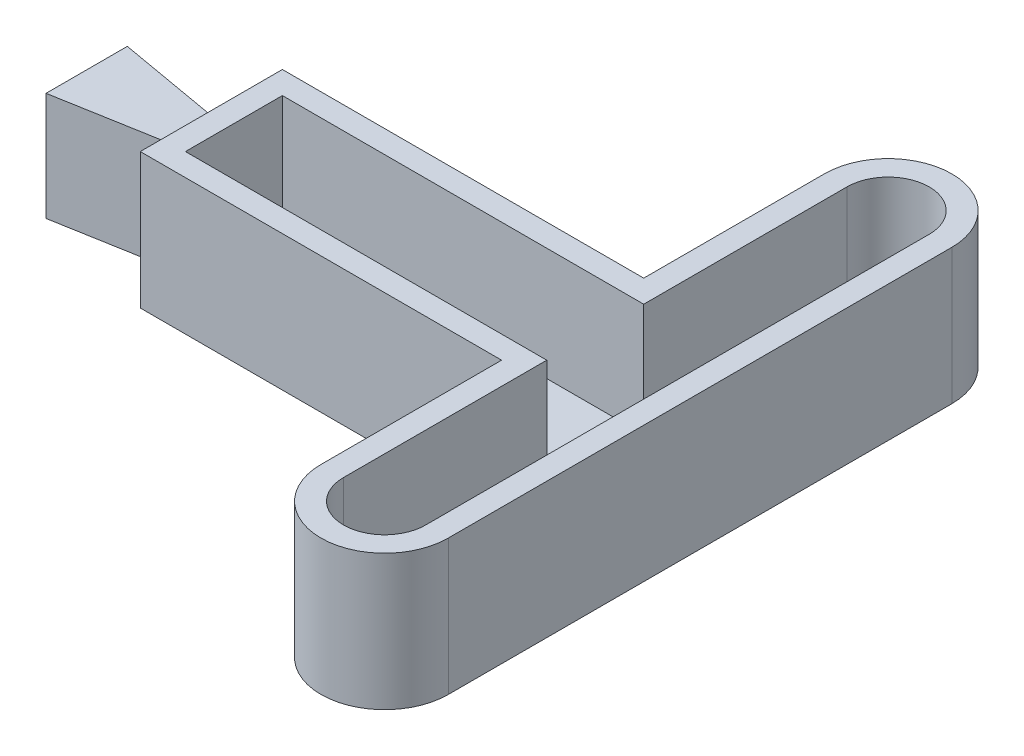
SolidWorks part; units mm, degrees
ref_plane "Front Plane" through (0, 0, 0) normal (0, 0, 1) x (1, 0, 0)
ref_plane "Top Plane" through (0, 0, 0) normal (0, 1, 0) x (1, 0, 0)
ref_plane "Right Plane" through (0, 0, 0) normal (1, 0, 0) x (0, 0, -1)
sketch "Sketch1" plane through (0, 0, 0) normal (0, 1, 0) x (1, 0, 0)
  line L0 (0, 11.43) -> (0, -11.43)
  line L1 (0, 11.43) -> (35.052, 5.2494)
  line L2 (0, -11.43) -> (35.052, -5.2494)
  line L3 (35.052, 5.2494) -> (35.052, 19.9814)
  line L4 (35.052, -5.2494) -> (35.052, -19.9814)
  line L5 (35.052, 5.2494) -> (35.052, -5.2494) construction
  line L6 (0, 0) -> (35.052, 0) construction
  line L7 (35.052, 19.9814) -> (136.652, 19.9814)
  line L8 (35.052, -19.9814) -> (136.652, -19.9814)
  line L9 (136.652, 19.9814) -> (136.652, 70.7814)
  line L10 (136.652, -19.9814) -> (136.652, -70.7814)
  line L12 (172.466, 70.7814) -> (172.466, -70.7814)
  arc A0 (172.466, 70.7814) -> (136.652, 70.7814) centre (154.559, 70.7814) ccw
  arc A1 (172.466, -70.7814) -> (136.652, -70.7814) centre (154.559, -70.7814) cw
  point P3 (0, 0)
  dimension "D1" = 22.86
  dimension "D2" = 35.052
  dimension "D3" = 80
  dimension "D4" = 80
  dimension "D5" = 39.9628
  dimension "D6" = 14.732
  dimension "D7" = 101.6
  dimension "D8" = 101.6
  dimension "D9" = 14.732
  dimension "D10" = 50.8
  dimension "D11" = 35.814
extrude "Boss-Extrude1" add sketch "Sketch1" along normal blind 38.1
sketch "Sketch5" plane through (0, 38.1, 0) normal (0, 1, 0) x (1, 0, 0)
  line L0 (0, -11.43) -> (0, 11.43)
  line L1 (0, -11.43) -> (35.052, -5.2494) construction
  line L2 (0, 11.43) -> (0, -11.43) construction
  line L3 (0, 11.43) -> (0.2105, 11.603)
  line L4 (35.052, 5.2494) -> (35.052, -5.2494)
  line L5 (35.052, -5.2494) -> (0, -11.43)
  line L6 (0.2105, 11.603) -> (35.052, 5.2494)
  dimension "D1" = 79.665
extrude "Cut-Extrude10" cut sketch "Sketch5" against normal blind 7.62
shell "Shell2" thickness 6.35 removed face at (120.2055, 38.1, 0)
